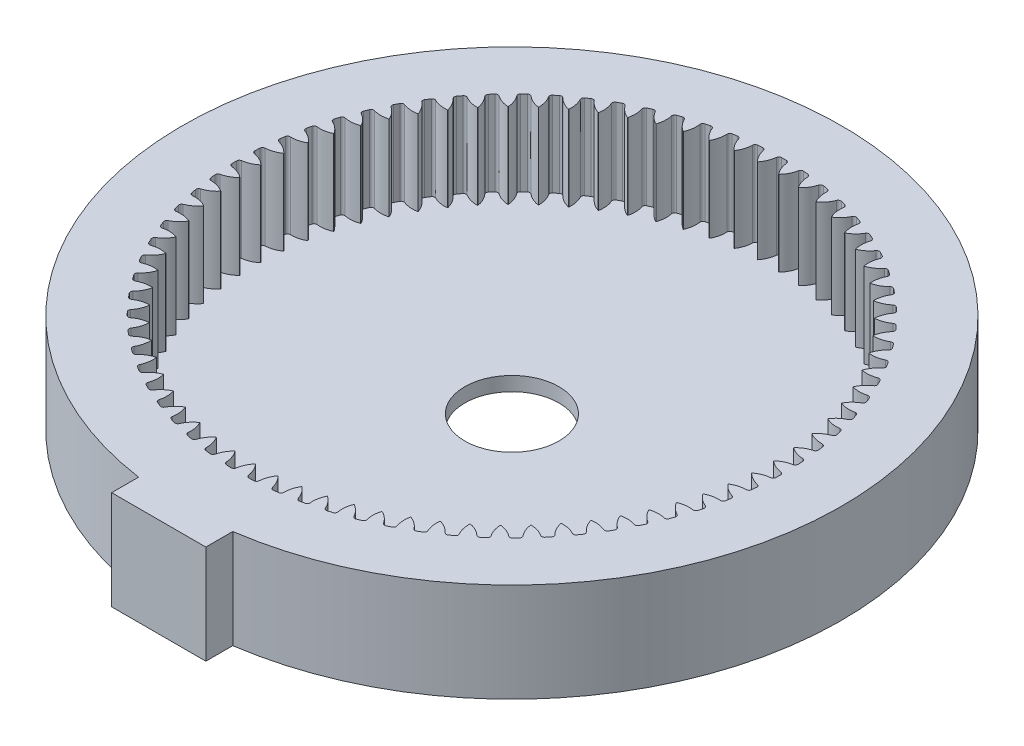
SolidWorks part; units mm, degrees
ref_plane "Front Plane" through (0, 0, 0) normal (0, 0, 1) x (1, 0, 0)
ref_plane "Top Plane" through (0, 0, 0) normal (0, 1, 0) x (1, 0, 0)
ref_plane "Right Plane" through (0, 0, 0) normal (1, 0, 0) x (0, 0, -1)
sketch "Sketch1" plane through (0, 0, 0) normal (0, 1, 0) x (1, 0, 0)
  circle A0 centre (0, 0) radius 54.47
  circle A1 centre (0, 0) radius 57.75 construction
  circle A2 centre (0, 0) radius 70
  dimension "D1" = 108.94
  dimension "D2" = 115.5
  dimension "D3" = 140
sketch "Sketch2" plane through (0, 0, 0) normal (0, 1, 0) x (1, 0, 0)
  line L0 (0, 0) -> (0, 57.75) construction
  line L1 (0, 0) -> (-1.0373, 54.3651) construction
  line L2 (-0.4046, 53.4923) -> (-5.5489, 67.6261) construction
  line L3 (0, 57.75) -> (0, 54.375) construction
  line L4 (0, 56.0625) -> (5.1259, 56.0625) construction
  arc A0 (1.0373, 54.3651) -> (-1.0373, 54.3651) centre (0, 0) ccw construction
  arc A1 (1.403, 56.2325) -> (-1.403, 56.2325) centre (0, 0) ccw construction
  arc A2 (2.2532, 57.706) -> (-1.0377, 57.7407) centre (0, 0) ccw construction
  arc A3 (-2.2532, 57.706) -> (-1.0373, 54.3651) centre (-6.5223, 54.2605) cw construction
  arc A4 (2.2532, 57.706) -> (1.0373, 54.3651) centre (6.5223, 54.2605) ccw construction
  arc A5 (2.2532, 54.419) -> (1.0373, 57.7599) centre (6.5223, 57.8645) cw
  arc A6 (-2.2532, 54.419) -> (-1.0373, 57.7599) centre (-6.5223, 57.8645) ccw
  arc A7 (2.2532, 54.419) -> (-2.2532, 54.419) centre (0, 0) ccw
  arc A8 (1.0373, 57.7599) -> (-1.0373, 57.7599) centre (0, 0) ccw
  arc A9 (-1.9424, 57.7173) -> (-2.2532, 57.706) centre (0, 0) ccw construction
  point P14 (-2.9767, 60.5592)
  point P17 (-1.3671, 56.1368)
  dimension "D1" = 115.5
  dimension "D2" = 112.5
  dimension "D3" = 3.375
  dimension "D4" = 20
  dimension "D5" = 2.8062
extrude "Boss-Extrude1" add sketch "Sketch1" along normal blind 18
extrude "Cut-Extrude1" cut sketch "Sketch2" along normal through all
fillet "Fillet1" radius 0.57 2 edges at (1.0373, 9, -57.7599) (-1.0373, 9, -57.7599)
pattern_circular "CirPattern1" count 75 over 360 about axis through (0, 18, 0) along (0, -1, 0) of "Cut-Extrude1", "Fillet1"
sketch "Sketch4" plane through (0, 0, 0) normal (0, 1, 0) x (1, 0, 0)
  circle A0 centre (0, 0) radius 70 construction
  circle A1 centre (0, 0) radius 70
extrude "Boss-Extrude2" add sketch "Sketch4" against normal blind 3
sketch "Sketch5" plane through (0, -3, 0) normal (0, -1, 0) x (1, 0, 0)
  circle A0 centre (0, 0) radius 10
  dimension "D1" = 20
extrude "Cut-Extrude2" cut sketch "Sketch5" against normal up to next
sketch "Sketch6" plane through (0, -3, 0) normal (0, -1, 0) x (1, 0, 0)
  line L0 (10, 66.7978) -> (-10, 66.7978)
  line L1 (0, 0) -> (-10, 0) construction
  line L2 (0, 0) -> (0, 75) construction
  line L3 (10, 75) -> (-10, 75)
  line L4 (-10, 0) -> (-10, 75) construction
  line L5 (-10, 66.7978) -> (-10, 75)
  line L6 (10, 66.7978) -> (10, 75)
  point P9 (0, 66.7978)
  dimension "D1" = 10
  dimension "D2" = 75
extrude "Boss-Extrude3" add sketch "Sketch6" against normal through all
scale "Scale1" scale about centroid uniform scaling yes scale factor 10
equation "\"num_teeth\"=75"
equation "\"outer_diameter\"= ( \"num_teeth\" + 2 ) * \"module\""
equation "\"module\"= 1.5"
equation "\"pitch_diameter\"= \"num_teeth\" * \"module\""
equation "\"arc_length\"= \"module\" * pi / 2 + \"backlash\""
equation "\"backlash\"= 0.3 * \"module\""
equation "\"Tooth_depth\"= IIF ( \"module\" <= 1.25 , \"module\" * 2.4 , \"module\" * 2.25 )"
equation "\"bore_diameter\"= 5"
equation "\"D2@Sketch1\"=\"outer_diameter\""
equation "\"D1@Sketch2\"=\"outer_diameter\""
equation "\"D2@Sketch2\"=\"pitch_diameter\""
equation "\"D3@Sketch2\"=\"Tooth_depth\""
equation "\"pitch_angle\"= 20"
equation "\"D4@Sketch2\"=\"pitch_angle\""
equation "\"D5@Sketch2\"=\"arc_length\""
equation "\"fillet_radius\"= 0.38 * \"module\""
equation "\"D1@Fillet1\"= \"fillet_radius\""
equation "\"D1@CirPattern1\"=\"num_teeth\""
equation "\"D1@Sketch3\"= \"outer_diameter\" + 5"
equation "\"D1@Fillet1\"=\"fillet_radius\""
